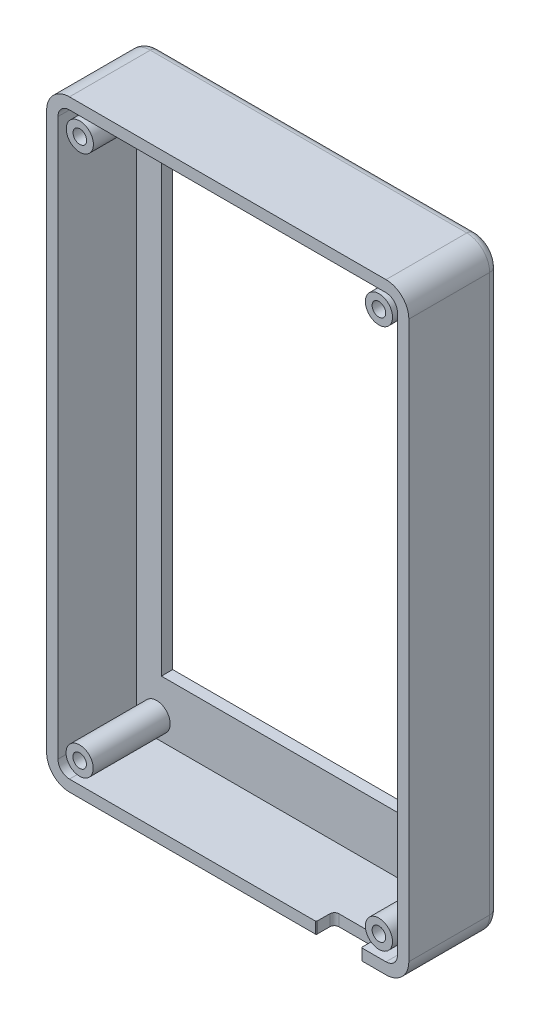
SolidWorks part; units mm, degrees
material "Plastique personnalisé"
ref_plane "Plan de face" through (0, 0, 0) normal (0, 0, 1) x (1, 0, 0)
ref_plane "Plan de dessus" through (0, 0, 0) normal (0, 1, 0) x (1, 0, 0)
ref_plane "Plan de droite" through (0, 0, 0) normal (1, 0, 0) x (0, 0, -1)
sketch "Esquisse1" plane through (0, 0, 0) normal (0, 0, 1) x (1, 0, 0)
  line L1 (-34.96, -64) -> (34.96, -64)
  line L2 (-37.5, -61.46) -> (-37.5, 61.46)
  line L3 (-34.96, 64) -> (34.96, 64)
  line L4 (37.5, -61.46) -> (37.5, 61.46)
  line L5 (-37.5, -64) -> (37.5, 64) construction
  line L6 (-37.5, 64) -> (37.5, -64) construction
  arc A0 (34.96, -64) -> (37.5, -61.46) centre (34.96, -61.46) ccw
  arc A1 (-34.96, -64) -> (-37.5, -61.46) centre (-34.96, -61.46) cw
  arc A2 (-37.5, 61.46) -> (-34.96, 64) centre (-34.96, 61.46) cw
  arc A3 (34.96, 64) -> (37.5, 61.46) centre (34.96, 61.46) cw
  point P0 (0, 0)
  dimension "D3" = 2.54
  dimension "D1" = 128
  dimension "D2" = 75
extrude "Boss.-Extru.1" add sketch "Esquisse1" along normal blind 17.35
shell "Coque1" thickness 2.5 removed face at (0, 0, 17.35) outward yes
fillet "Congé1" radius 2 8 edges at (40, 0, -2.5) (38.5238, -65.0238, -2.5) (0, -66.5, -2.5) (-38.5238, -65.0238, -2.5) (-40, 0, -2.5) (-38.5238, 65.0238, -2.5) (0, 66.5, -2.5) (38.5238, 65.0238, -2.5)
sketch "Esquisse3" plane through (0, 0, 0) normal (0, 0, 1) x (1, 0, 0)
  circle A0 centre (-33.02, 59.69) radius 1.5
  circle A1 centre (-33.02, 59.69) radius 3
  circle A2 centre (33.0465, 59.69) radius 1.5
  circle A3 centre (33.0465, 59.69) radius 3
  circle A4 centre (-33.06, -59.69) radius 3
  circle A5 centre (-33.06, -59.69) radius 1.5
  circle A6 centre (33.0465, -59.759) radius 3
  circle A7 centre (33.0465, -59.759) radius 1.5
  dimension "D1" = 3
  dimension "D2" = 3
extrude "Boss.-Extru.2" add sketch "Esquisse3" along normal blind 17
sketch "Esquisse5" plane through (0, 0, 0) normal (0, 0, 1) x (1, 0, 0)
  circle A0 centre (-33.02, 59.69) radius 1.5
  circle A1 centre (33.0465, 59.69) radius 1.5
  circle A2 centre (33.0465, -59.759) radius 1.5
  circle A3 centre (-33.06, -59.69) radius 1.5
extrude "Enlèv. mat.-Extru.3" cut sketch "Esquisse5" against normal through all both and the other way through all
sketch "Esquisse6" plane through (0, 0, -2.5) normal (0, 0, -1) x (-1, 0, 0)
  line L0 (0, -66.5) -> (0, -51.5) construction
  line L2 (34.96, -66.5) -> (-34.96, -66.5) construction
  line L4 (-40, -51.5) -> (40, -51.5) construction
  line L6 (0, 66.5) -> (0, 57) construction
  line L7 (-34.96, 66.5) -> (34.96, 66.5) construction
  line L8 (-40, -61.46) -> (-40, 61.46) construction
  line L9 (40, 61.46) -> (40, -61.46) construction
  line L10 (-40, 57) -> (40, 57) construction
  line L11 (-40, 0) -> (-28, 0) construction
  line L12 (40, 0) -> (32, 0) construction
  line L13 (32, 0) -> (32, -51.5) construction
  line L14 (-28, 0) -> (-28, 57) construction
  line L16 (-28, 57) -> (32, 57)
  line L17 (-28, 57) -> (-28, -51.5)
  line L18 (-28, -51.5) -> (32, -51.5)
  line L19 (32, 57) -> (32, -51.5)
  dimension "D1" = 15
  dimension "D2" = 12
  dimension "D3" = 8
extrude "Enlèv. mat.-Extru.4" cut sketch "Esquisse6" against normal blind 10
sketch "Esquisse7" plane through (0, 0, 0) normal (0, 0, 1) x (1, 0, 0)
  line L0 (-32, 56.8687) -> (28, -51.5) construction
sketch "Esquisse8" plane through (0, -66.5, 0) normal (0, -1, 0) x (-1, 0, 0)
  line L0 (34.96, -17.35) -> (-34.96, -17.35) construction
  line L1 (-29.5029, -17.35) -> (-19.5514, -17.35)
  line L2 (-29.5029, -17.35) -> (-29.5029, -14.35)
  line L3 (-28.5029, -13.35) -> (-20.5514, -13.35)
  line L4 (-19.5514, -17.35) -> (-19.5514, -14.35)
  arc A0 (-20.5514, -13.35) -> (-19.5514, -14.35) centre (-20.5514, -14.35) cw
  arc A1 (-29.5029, -14.35) -> (-28.5029, -13.35) centre (-28.5029, -14.35) cw
  point P10 (-29.5029, -13.35)
  dimension "D2" = 1
  dimension "D1" = 4
extrude "Enlèv. mat.-Extru.5" cut sketch "Esquisse8" against normal blind 10
fillet "Congé2" radius 0.2 2 edges at (29.5029, -65.25, 17.35) (19.5514, -65.25, 17.35)
